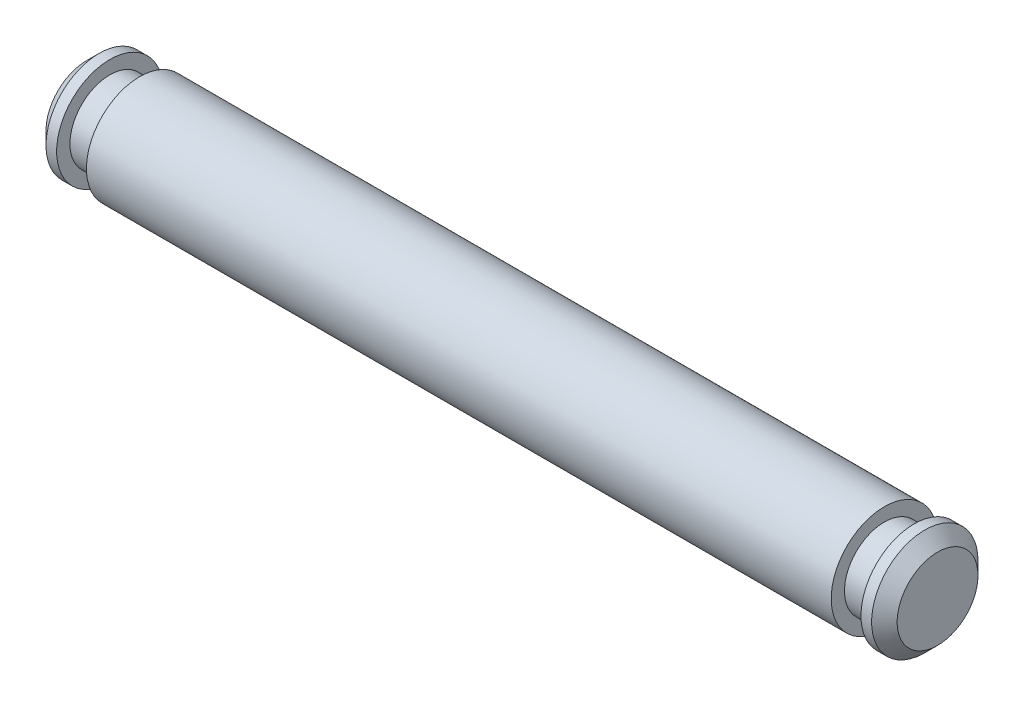
SolidWorks part; units mm, degrees
ref_plane "Front Plane" through (0, 0, 0) normal (0, 0, 1) x (1, 0, 0)
ref_plane "Top Plane" through (0, 0, 0) normal (0, 1, 0) x (1, 0, 0)
ref_plane "Right Plane" through (0, 0, 0) normal (1, 0, 0) x (0, 0, -1)
sketch "Sketch1" plane through (0, 0, 0) normal (0, 0, 1) x (1, 0, 0)
  line L0 (0, 0) -> (50.8, 0)
  line L1 (50.8, 0) -> (50.8, 2.413)
  line L2 (50.8, 2.413) -> (50.038, 3.175)
  line L3 (50.038, 3.175) -> (49.403, 3.175)
  line L4 (49.403, 3.175) -> (49.403, 2.3813)
  line L5 (49.403, 2.3813) -> (47.625, 2.3813)
  line L6 (47.625, 2.3813) -> (47.625, 3.175)
  line L7 (47.625, 3.175) -> (3.175, 3.175)
  line L8 (3.175, 3.175) -> (3.175, 2.3813)
  line L9 (3.175, 2.3813) -> (1.397, 2.3813)
  line L10 (1.397, 2.3813) -> (1.397, 3.175)
  line L11 (1.397, 3.175) -> (0.762, 3.175)
  line L12 (0.762, 3.175) -> (0, 2.413)
  line L13 (0, 2.413) -> (0, 0)
  line L14 (0, 0) -> (-4.8683, 0) construction
  point P3 (0, 0)
  dimension "D1" = 6.35
  dimension "D2" = 50.8
  dimension "D3" = 0.762
  dimension "D4" = 1.778
  dimension "D5" = 44.45
  dimension "D6" = 4.7625
revolve "Revolve1" add sketch "Sketch1" angle 360 about L14
